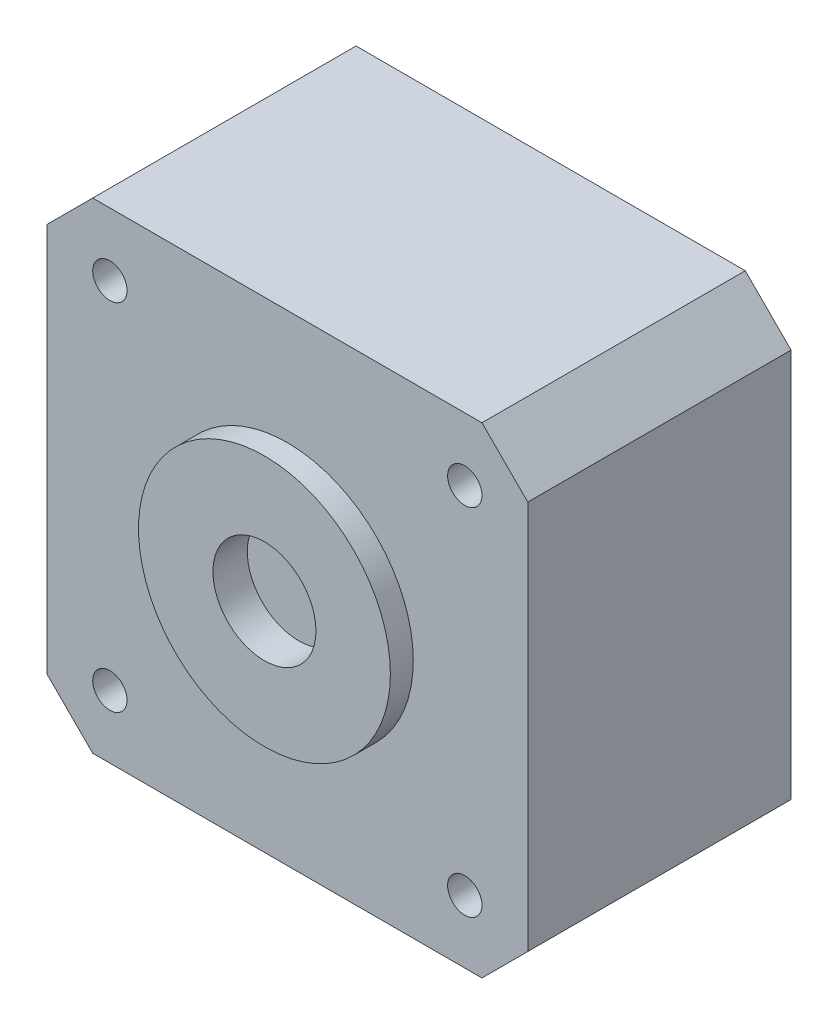
SolidWorks part; units mm, degrees
ref_plane "前视基准面" through (0, 0, 0) normal (0, 0, 1) x (1, 0, 0)
ref_plane "上视基准面" through (0, 0, 0) normal (0, 1, 0) x (1, 0, 0)
ref_plane "右视基准面" through (0, 0, 0) normal (1, 0, 0) x (0, 0, -1)
sketch "草图1" plane through (0, 0, 0) normal (0, 0, 1) x (1, 0, 0)
  line L0 (-1000, 0) -> (49000, 0) construction
  line L1 (-21, -21) -> (21, -21)
  line L2 (-21, -21) -> (-21, 21)
  line L3 (-21, 21) -> (21, 21)
  line L4 (21, -21) -> (21, 21)
  line L5 (-21, -21) -> (21, 21) construction
  line L6 (-21, 21) -> (21, -21) construction
  line L7 (-17, 21) -> (-21, 17)
  line L8 (0, -1000) -> (0, 49000) construction
  line L9 (17, 21) -> (21, 17)
  line L10 (17, -21) -> (21, -17)
  line L11 (-17, -21) -> (-21, -17)
  line L12 (-1.5, 2) -> (1.5, 2)
  circle A0 centre (0, 0) radius 11
  circle A1 centre (-15.5, 15.5) radius 1.5
  circle A2 centre (15.5, 15.5) radius 1.5
  circle A3 centre (-15.5, -15.5) radius 1.5
  circle A4 centre (15.5, -15.5) radius 1.5
  circle A5 centre (0, 0) radius 2.5
  point P0 (0, 0)
  dimension "D3" = 22
  dimension "D4" = 3
  dimension "D5" = 3
  dimension "D6" = 31
  dimension "D7" = 5
  dimension "D1" = 42
  dimension "D2" = 42
  dimension "D8" = 4
  dimension "D9" = 4
  dimension "D10" = 2
extrude "凸台-拉伸1" add sketch "草图1" along normal blind 23 contours L11 L1 L10 L4 L9 L3 L7 L2 A3 A2 A1 A0 A4 | A0 A5 | A5 region at (-18.58, -18.58, 0) region at (-10.6889, 0, 0)
extrude "凸台-拉伸2" add sketch "草图1<3>" along normal blind 19.5 contours A1 | A2 | A3 | A4 region at (-15.5, 15.5, 0)
sketch "草图1<3>" plane through (0, 0, 0) normal (0, 0, 1) x (1, 0, 0) same geometry as "草图1"
extrude "凸台-拉伸4" add sketch "草图1<6>" along normal blind 25 contours A0 A5 | L12 A5 | L12 A5 region at (0, 2.2018, 0) region at (0, -0.1209, 0) region at (-10.6889, 0, 0)
sketch "草图1<6>" plane through (0, 0, 0) normal (0, 0, 1) x (1, 0, 0) same geometry as "草图1"
sketch "草图2" plane through (0, 0, 25) normal (0, 0, 1) x (1, 0, 0)
  circle A0 centre (0, 0) radius 4.5
  dimension "D1" = 9
extrude "切除-拉伸1" cut sketch "草图2" against normal blind 3
